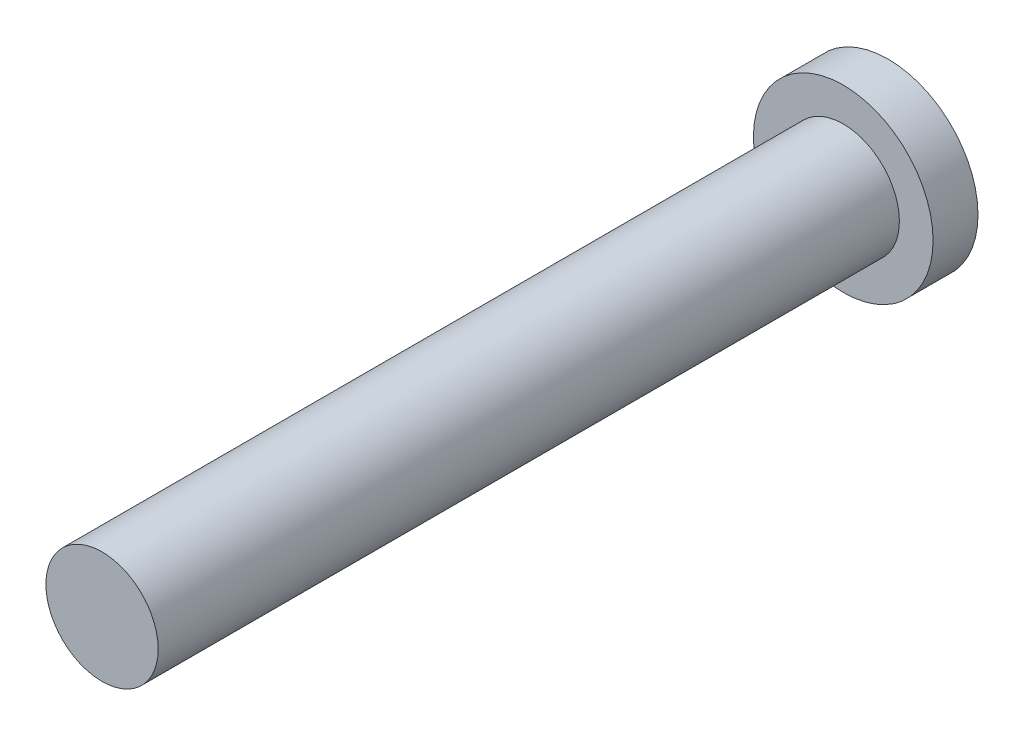
SolidWorks part; units mm, degrees
ref_plane "Plan de face" through (0, 0, 0) normal (0, 0, 1) x (1, 0, 0)
ref_plane "Plan de dessus" through (0, 0, 0) normal (0, 1, 0) x (1, 0, 0)
ref_plane "Plan de droite" through (0, 0, 0) normal (1, 0, 0) x (0, 0, -1)
sketch "Esquisse1" plane through (0, 0, 0) normal (0, 0, 1) x (1, 0, 0)
  circle A0 centre (0, 0) radius 4
  circle A1 centre (0, 0) radius 2.5
extrude "Boss.-Extru.1" add sketch "Esquisse1" along normal blind 2
extrude "Boss.-Extru.2" add sketch "Esquisse1<2>" along normal blind 35 contours A1 region at (0, 0, 0)
sketch "Esquisse1<2>" plane through (0, 0, 0) normal (0, 0, 1) x (1, 0, 0) same geometry as "Esquisse1"
